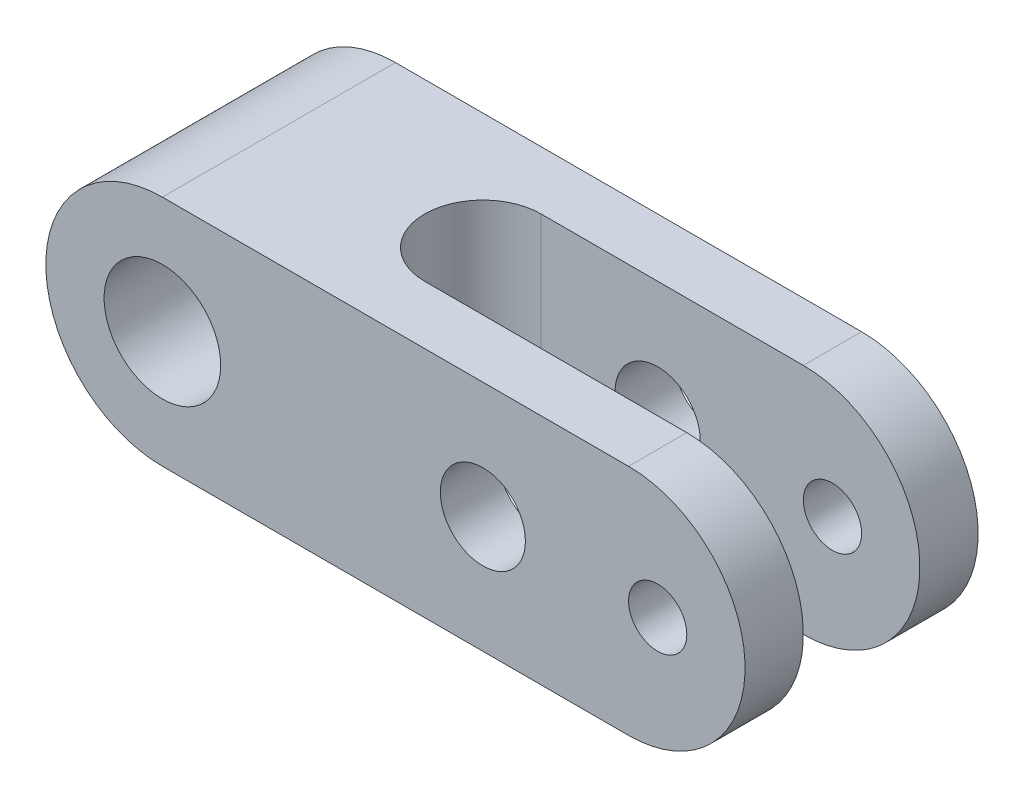
SolidWorks part; units mm, degrees
material "Custom Plastic"
ref_plane "X-Y Datum" through (0, 0, 0) normal (0, 0, 1) x (1, 0, 0)
ref_plane "X-Z Datum" through (0, 0, 0) normal (0, 1, 0) x (1, 0, 0)
ref_plane "Y-Z Datum" through (0, 0, 0) normal (1, 0, 0) x (0, 0, -1)
sketch "Sketch1" plane through (0, 0, 0) normal (0, 0, 1) x (1, 0, 0)
  line L0 (-25.4, 0) -> (25.4, 0) construction
  line L1 (-25.4, 12.7) -> (25.4, 12.7)
  line L2 (-25.4, -12.7) -> (25.4, -12.7)
  arc A0 (-25.4, 12.7) -> (-25.4, -12.7) centre (-25.4, 0) ccw
  arc A1 (25.4, -12.7) -> (25.4, 12.7) centre (25.4, 0) ccw
  point P2 (0, 0)
  dimension "D1" = 25.4
  dimension "D2" = 50.8
extrude "Boss-Extrude1" add sketch "Sketch1" along normal mid plane 25.4
sketch "Sketch2" plane through (0, 0, 12.7) normal (0, 0, 1) x (1, 0, 0)
  circle A0 centre (28.575, 0) radius 3.175
  circle A1 centre (9.525, 0) radius 4.6355
  circle A2 centre (-25.4, 0) radius 6.35
  dimension "D1" = 6.35
  dimension "D2" = 9.271
  dimension "D5" = 12.7
  dimension "D3" = 19.05
  dimension "D4" = 9.525
  dimension "D6" = 25.4
extrude "Cut-Extrude1" cut sketch "Sketch2" against normal up to surface (25.4 mm away) up to face at (0, 0, -12.7)
sketch "Sketch3" plane through (0, 12.7, 0) normal (0, 1, 0) x (1, 0, 0)
  line L0 (38.1, -12.7) -> (38.1, 12.7) construction
  line L1 (-9.525, 6.35) -> (38.1, 6.35)
  line L2 (-9.525, 6.35) -> (-9.525, -6.35)
  line L3 (-9.525, -6.35) -> (38.1, -6.35)
  line L4 (38.1, 6.35) -> (38.1, -6.35)
  line L5 (25.4, 12.7) -> (-25.4, 12.7) construction
  dimension "D1" = 12.7
  dimension "D2" = 6.35
  dimension "D3" = 47.625
extrude "Cut-Extrude2" cut sketch "Sketch3" along direction (0, 1, 0) on the side against the normal up to surface (25.4 mm away) up to face at (0, -12.7, 0)
fillet "Fillet1" 2 edges at (-9.525, 0, -6.35) (-9.525, 0, 6.35) type full round first side face at (25.4, 0, -6.35) second side face at (31.75, 0, 6.35) middle face at (-9.525, 0, 0)
sketch3d "3DSketch1"
  line L0 (28.575, 0, 12.7) -> (28.575, 0, -12.7) construction
  line L6 (28.575, 0, -12.7) -> (28.575, 0, -6.35) construction
  point P8 (28.575, 0, 0)
  point P9 (0, 0, 0)
  point P13 (0, 0, 0)
  point P14 (0, 0, 0)
